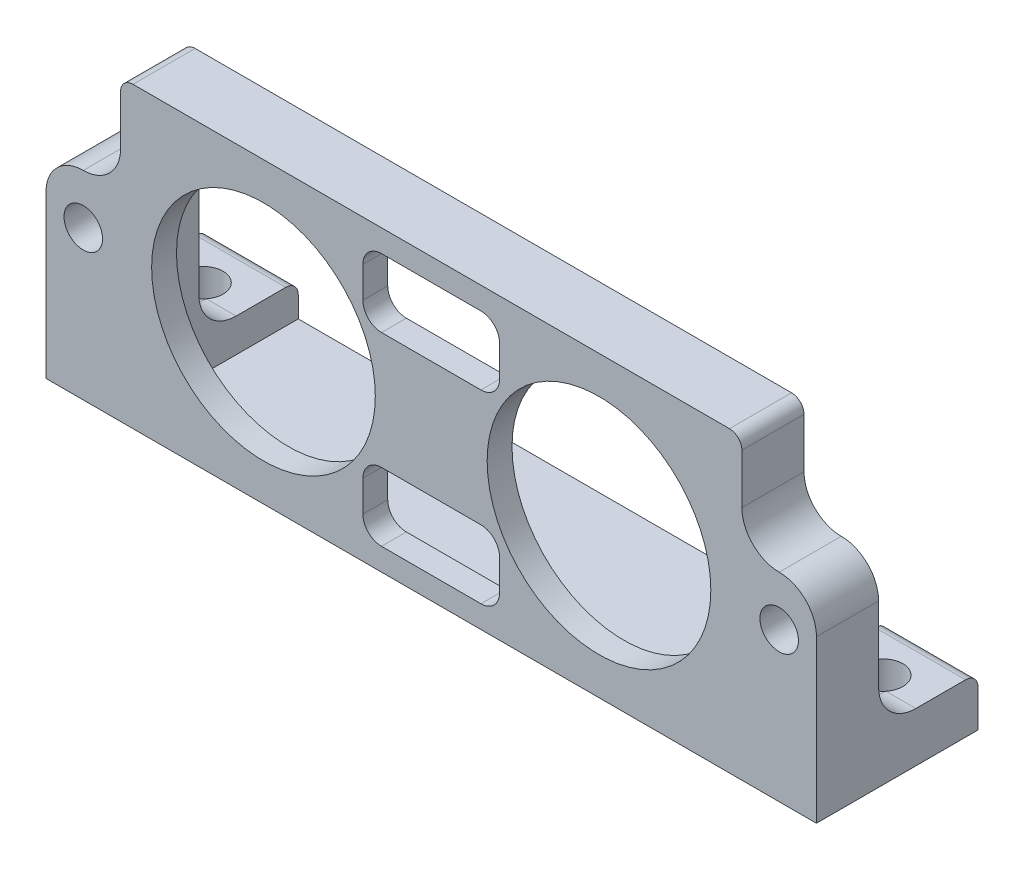
SolidWorks part; units mm, degrees
material "ABS"
ref_plane "Спереди" through (0, 0, 0) normal (0, 0, 1) x (1, 0, 0)
ref_plane "Сверху" through (0, 0, 0) normal (0, 1, 0) x (1, 0, 0)
ref_plane "Справа" through (0, 0, 0) normal (1, 0, 0) x (0, 0, -1)
sketch "Sketch1" plane through (0, 0, 0) normal (0, 0, 1) x (1, 0, 0)
  line L1 (-25, 12) -> (25, 12)
  line L2 (-25, 12) -> (-25, 4)
  line L3 (-25, -12) -> (25, -12)
  line L4 (25, 12) -> (25, 4)
  line L5 (-25, 12) -> (25, -12) construction
  line L6 (-25, -12) -> (25, 12) construction
  line L8 (-31, 4) -> (-25, 4)
  line L9 (-31, 4) -> (-31, -12)
  line L10 (-31, -12) -> (-25, -12)
  line L11 (0, 0) -> (0, 12) construction
  line L12 (-31, 4) -> (-25, -12) construction
  line L13 (-31, -12) -> (-25, 4) construction
  line L14 (31, -12) -> (25, -12)
  line L15 (31, 4) -> (31, -12)
  line L16 (31, 4) -> (25, 4)
  point P0 (0, 0)
  dimension "D1" = 24
  dimension "D2" = 50
  dimension "D3" = 16
  dimension "D4" = 6
extrude "Boss-Extrude1" add sketch "Sketch1" along normal blind 2
sketch "Sketch4" plane through (0, 0, 0) normal (0, 0, -1) x (-1, 0, 0)
  line L0 (-25, 12) -> (-25, 4)
  line L1 (31, -12) -> (-31, -12) construction
  line L2 (-25, 12) -> (25, 12)
  line L3 (25, 12) -> (25, 4)
  line L4 (25, -12) -> (-25, -12)
  line L6 (-23.7, 10.7) -> (23.7, 10.7)
  line L7 (-23.7, 10.7) -> (-23.7, -10.7)
  line L8 (-23.7, -10.7) -> (23.7, -10.7)
  line L9 (23.7, 10.7) -> (23.7, -10.7)
  line L10 (-23.7, 10.7) -> (23.7, -10.7) construction
  line L11 (-23.7, -10.7) -> (23.7, 10.7) construction
  line L12 (31, 4) -> (25, 4)
  line L13 (31, 4) -> (31, -12)
  line L14 (31, -12) -> (25, -12)
  line L16 (-31, 4) -> (-25, 4)
  line L17 (-31, 4) -> (-31, -12)
  line L18 (-31, -12) -> (-25, -12)
  point P8 (0, 0)
  dimension "D1" = 1.3
  dimension "D2" = 1.3
extrude "Boss-Extrude2" add sketch "Sketch4" along normal blind 3
sketch "Sketch2" plane through (0, 0, 2) normal (0, 0, 1) x (1, 0, 0)
  line L0 (0, 0) -> (13.5, 0) construction
  line L1 (0, 0) -> (-13.5, 0) construction
  line L2 (0, 7.45) -> (0, 0) construction
  line L3 (-4, 10.2) -> (4, 10.2)
  line L4 (-5.5, 8.7) -> (-5.5, 6.2)
  line L5 (-4, 4.7) -> (4, 4.7)
  line L6 (5.5, 8.7) -> (5.5, 6.2)
  line L7 (-5.5, 10.2) -> (5.5, 4.7) construction
  line L8 (-5.5, 4.7) -> (5.5, 10.2) construction
  line L9 (25, 12) -> (-25, 12) construction
  line L10 (-5.5, -8.7) -> (-5.5, -6.2)
  line L11 (-4, -4.7) -> (4, -4.7)
  line L12 (-4, -10.2) -> (4, -10.2)
  line L13 (5.5, -8.7) -> (5.5, -6.2)
  line L14 (-13.5, 0) -> (-28, 0) construction
  line L16 (-31, 4) -> (-31, -12) construction
  circle A0 centre (-13.5, 0) radius 9
  circle A1 centre (13.5, 0) radius 9
  arc A2 (4, -4.7) -> (5.5, -6.2) centre (4, -6.2) cw
  arc A3 (4, -10.2) -> (5.5, -8.7) centre (4, -8.7) ccw
  arc A4 (-5.5, -8.7) -> (-4, -10.2) centre (-4, -8.7) ccw
  arc A5 (-5.5, -6.2) -> (-4, -4.7) centre (-4, -6.2) cw
  arc A6 (4, 10.2) -> (5.5, 8.7) centre (4, 8.7) cw
  arc A7 (4, 4.7) -> (5.5, 6.2) centre (4, 6.2) ccw
  arc A8 (-4, 10.2) -> (-5.5, 8.7) centre (-4, 8.7) ccw
  arc A9 (-5.5, 6.2) -> (-4, 4.7) centre (-4, 6.2) ccw
  circle A10 centre (-28, 0) radius 1.55
  circle A11 centre (28, 0) radius 1.55
  point P6 (0, 7.45)
  point P20 (5.5, -4.7)
  point P23 (5.5, -10.2)
  point P26 (-5.5, -10.2)
  point P29 (-5.5, -4.7)
  dimension "D1" = 18
  dimension "D6" = 1.5
  dimension "D7" = 3.1
  dimension "D2" = 27
  dimension "D3" = 11
  dimension "D4" = 5.5
  dimension "D5" = 1.8
  dimension "D8" = 3
extrude "Cut-Extrude1" cut sketch "Sketch2" against normal through all
sketch "Sketch5" plane through (0, 0, -3) normal (0, 0, -1) x (-1, 0, 0)
  line L0 (-23.7, 10.7) -> (-23.7, -10.7) construction
  line L2 (-31, -12) -> (-31, -8)
  line L3 (-31, -8) -> (-23.7, -8)
  line L4 (-23.7, -10.7) -> (-23.7, -8)
  line L5 (23.7, -10.7) -> (23.7, 10.7) construction
  line L7 (31, -12) -> (31, -8)
  line L8 (31, -8) -> (23.7, -8)
  line L9 (23.7, -10.7) -> (23.7, -8)
  line L10 (23.7, -10.7) -> (-23.7, -10.7)
  line L11 (-23.7, -10.7) -> (23.7, -10.7) construction
  line L12 (-31, -12) -> (31, -12)
  dimension "D1" = 4
extrude "Boss-Extrude3" add sketch "Sketch5" along normal blind 8
sketch "Sketch6" plane through (0, -8, 0) normal (0, 1, 0) x (1, 0, 0)
  line L0 (-27.35, 11) -> (-27.35, 7) construction
  line L1 (-31, 11) -> (-23.7, 11) construction
  line L2 (0, 11) -> (0, 0) construction
  line L3 (-23.7, 11) -> (23.7, 11) construction
  circle A0 centre (-27.35, 7) radius 1.6
  circle A1 centre (27.35, 7) radius 1.6
  dimension "D1" = 3.2
  dimension "D2" = 4
extrude "Cut-Extrude2" cut sketch "Sketch6" against normal through all
fillet "Fillet4" radius 3 2 edges
fillet "Fillet5" radius 3 4 edges at (31, 4, -0.5) (25, 4, -0.5) (-31, 4, -0.5) (-25, 4, -0.5)
fillet "Fillet6" radius 1 4 edges at (-27.35, -8, -11) (27.35, -8, -11) (-25, 12, -0.5) (25, 12, -0.5)
